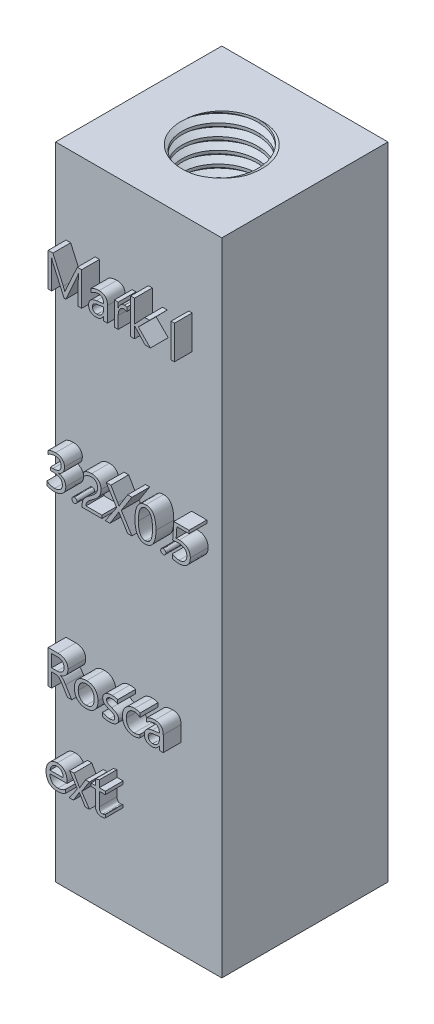
SolidWorks part; units mm, degrees
ref_plane "Alzado" through (0, 0, 0) normal (0, 0, 1) x (1, 0, 0)
ref_plane "Planta" through (0, 0, 0) normal (0, 1, 0) x (1, 0, 0)
ref_plane "Vista lateral" through (0, 0, 0) normal (1, 0, 0) x (0, 0, -1)
sketch "Croquis1" plane through (0, 0, 0) normal (0, 1, 0) x (1, 0, 0)
  line L1 (-3.5, 3.5) -> (3.5, 3.5)
  line L2 (-3.5, 3.5) -> (-3.5, -3.5)
  line L3 (-3.5, -3.5) -> (3.5, -3.5)
  line L4 (3.5, 3.5) -> (3.5, -3.5)
  line L5 (-3.5, 3.5) -> (3.5, -3.5) construction
  line L6 (-3.5, -3.5) -> (3.5, 3.5) construction
  circle A0 centre (0, 0) radius 1.6
  point P0 (0, 0)
  dimension "D1" = 3.2
  dimension "7" = 7
extrude "Saliente-Extruir1" add sketch "Croquis1" along normal blind 27
sketch "Croquis2" plane through (0, 0, 3.5) normal (0, 0, 1) x (1, 0, 0)
  text T0 "Mark I\r\n \r\n3.2X0.5\r\n\r\nRosca\r\next" font "@Adobe Heiti Std R" height in points 5
split line "Línea de partición1"
extrude "Saliente-Extruir2" add sketch "Croquis2<2>" along normal blind 0.75
sketch "Croquis2<2>" plane through (0, 0, 3.5) normal (0, 0, 1) x (1, 0, 0) same geometry as "Croquis2"
thread "Rosca1" pitch 0.5 method cut profile "Perfil de rosca1" start angle 0, offset 1, length 25, pitch 0.5, diameter 3.2
ref_plane "Plano1" through (-1.6, 28, 0) normal (0, 0, 1) x (-1, 0, 0)
sketch "Perfil de rosca1" plane through (-1.6, 28, 0) normal (0, 0, 1) x (-1, 0, 0)
  line L0 (0, 0) -> (0, 0.5) construction
  line L1 (0, 0) -> (0.2706, 0.1562)
  line L2 (0.2706, 0.1562) -> (0.2706, 0.2187)
  line L3 (0.2706, 0.2187) -> (0, 0.375)
  line L4 (0.2706, 0.1875) -> (0, 0.1875) construction
  line L11 (0, 0) -> (0, 0.375)
  point P2 (0, 0)
  dimension "Pitch" = 0.5
  dimension "Profile_Angle" = 60
  dimension "Profile_Land" = 0.0625
  dimension "Profile_Height" = 0.2706
